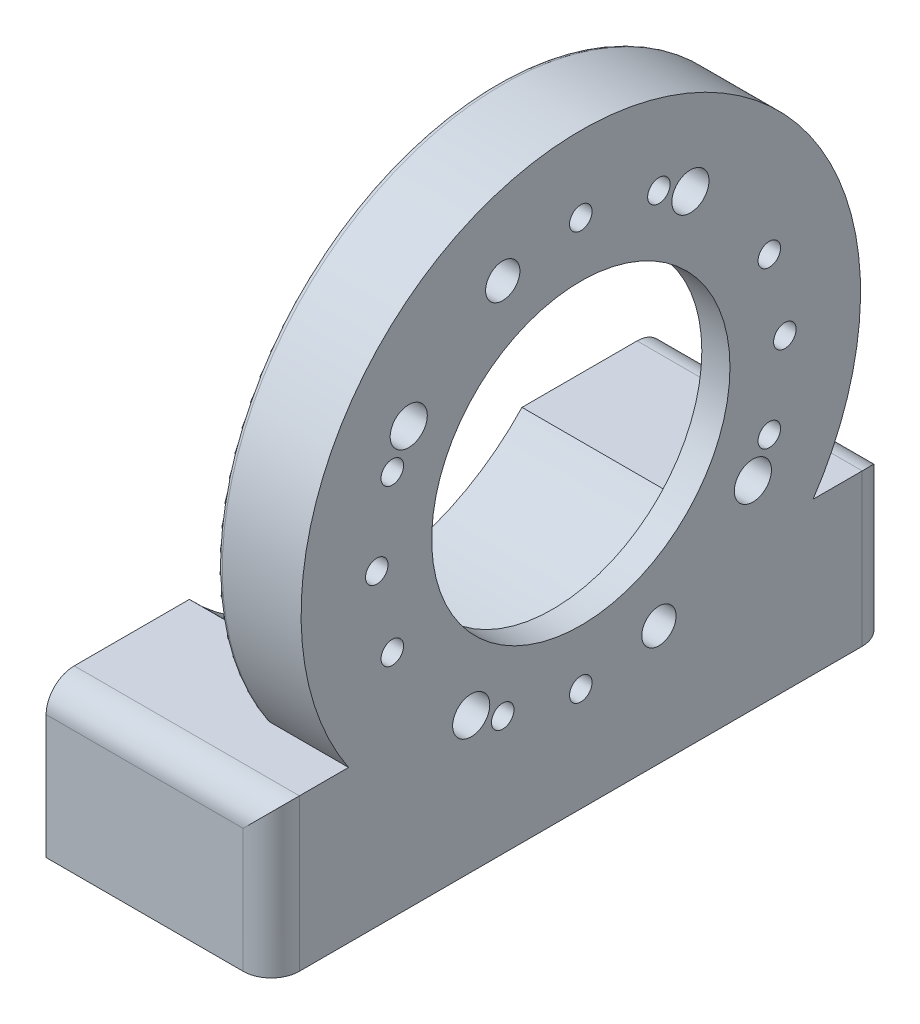
SolidWorks part; units mm, degrees
ref_plane "Front Plane" through (0, 0, 0) normal (0, 0, 1) x (1, 0, 0)
ref_plane "Top Plane" through (0, 0, 0) normal (0, 1, 0) x (1, 0, 0)
ref_plane "Right Plane" through (0, 0, 0) normal (1, 0, 0) x (0, 0, -1)
sketch "Sketch2" plane through (0, 0, 0) normal (1, 0, 0) x (0, 0, -1)
  arc A0 (-32.0764, 15.2865) -> (-34.9048, 12.4581) centre (-33.4906, 13.8723) ccw
  arc A1 (-34.9048, 12.4581) -> (-32.0764, 15.2865) centre (-33.4906, 13.8723) ccw
  arc A74 (-20.5317, -3.7195) -> (-23.1344, -1.6907) centre (-21.8331, -2.7051) ccw
  arc A75 (-23.1344, -1.6907) -> (-20.5317, -3.7195) centre (-21.8331, -2.7051) ccw
  arc A76 (-16.2541, -14.2736) -> (-18.8568, -12.2448) centre (-17.5554, -13.2592) ccw
  arc A77 (-18.8568, -12.2448) -> (-16.2541, -14.2736) centre (-17.5554, -13.2592) ccw
  arc A78 (-7.2725, -21.275) -> (-9.8752, -19.2461) centre (-8.5738, -20.2605) ccw
  arc A79 (-9.8752, -19.2461) -> (-7.2725, -21.275) centre (-8.5738, -20.2605) ccw
  arc A80 (4.0065, -22.8475) -> (1.4038, -20.8186) centre (2.7051, -21.8331) ccw
  arc A81 (1.4038, -20.8186) -> (4.0065, -22.8475) centre (2.7051, -21.8331) ccw
  arc A82 (14.5606, -18.5698) -> (11.9579, -16.541) centre (13.2592, -17.5554) ccw
  arc A83 (11.9579, -16.541) -> (14.5606, -18.5698) centre (13.2592, -17.5554) ccw
  arc A84 (21.5619, -9.5882) -> (18.9592, -7.5594) centre (20.2605, -8.5738) ccw
  arc A85 (18.9592, -7.5594) -> (21.5619, -9.5882) centre (20.2605, -8.5738) ccw
  arc A86 (23.1344, 1.6907) -> (20.5317, 3.7195) centre (21.8331, 2.7051) ccw
  arc A87 (20.5317, 3.7195) -> (23.1344, 1.6907) centre (21.8331, 2.7051) ccw
  arc A88 (18.8568, 12.2448) -> (16.2541, 14.2736) centre (17.5554, 13.2592) ccw
  arc A89 (16.2541, 14.2736) -> (18.8568, 12.2448) centre (17.5554, 13.2592) ccw
  arc A90 (9.8752, 19.2461) -> (7.2725, 21.275) centre (8.5738, 20.2605) ccw
  arc A91 (7.2725, 21.275) -> (9.8752, 19.2461) centre (8.5738, 20.2605) ccw
  arc A92 (-1.4038, 20.8186) -> (-4.0065, 22.8475) centre (-2.7051, 21.8331) ccw
  arc A93 (-4.0065, 22.8475) -> (-1.4038, 20.8186) centre (-2.7051, 21.8331) ccw
  arc A94 (-11.9579, 16.541) -> (-14.5606, 18.5698) centre (-13.2592, 17.5554) ccw
  arc A95 (-14.5606, 18.5698) -> (-11.9579, 16.541) centre (-13.2592, 17.5554) ccw
  arc A96 (-18.9592, 7.5594) -> (-21.5619, 9.5882) centre (-20.2605, 8.5738) ccw
  arc A97 (-21.5619, 9.5882) -> (-18.9592, 7.5594) centre (-20.2605, 8.5738) ccw
  arc A98 (-17.1437, -28.2395) -> (-21.8106, -32.9064) centre (-19.4771, -30.5729) ccw
  arc A99 (-21.8106, -32.9064) -> (-17.1437, -28.2395) centre (-19.4771, -30.5729) ccw
  arc A102 (32.9064, -17.1437) -> (28.2395, -21.8106) centre (30.5729, -19.4771) ccw
  arc A103 (28.2395, -21.8106) -> (32.9064, -17.1437) centre (30.5729, -19.4771) ccw
  arc A104 (21.8106, 32.9064) -> (17.1437, 28.2395) centre (19.4771, 30.5729) ccw
  arc A105 (17.1437, 28.2395) -> (21.8106, 32.9064) centre (19.4771, 30.5729) ccw
  arc A108 (-28.2395, 21.8106) -> (-32.9064, 17.1437) centre (-30.5729, 19.4771) ccw
  arc A109 (-32.9064, 17.1437) -> (-28.2395, 21.8106) centre (-30.5729, 19.4771) ccw
  arc A110 (-20.9002, 16.2921) -> (20.9002, -16.2921) centre (0, 0) ccw
  arc A111 (20.9002, -16.2921) -> (-20.9002, 16.2921) centre (0, 0) ccw
  circle A112 centre (0, 0) radius 40.5
  arc A113 (16.029, -31.334) -> (11.7156, -35.6473) centre (13.8723, -33.4906) ccw
  arc A114 (-37.6642, -1.4142) -> (-34.8358, 1.4142) centre (-36.25, 0) ccw
  arc A115 (-34.8358, 1.4142) -> (-37.6642, -1.4142) centre (-36.25, 0) ccw
  arc A116 (-34.9048, -15.2865) -> (-32.0764, -12.4581) centre (-33.4906, -13.8723) ccw
  arc A117 (-32.0764, -12.4581) -> (-34.9048, -15.2865) centre (-33.4906, -13.8723) ccw
  arc A118 (-12.4581, -32.0764) -> (-15.2865, -34.9048) centre (-13.8723, -33.4906) ccw
  arc A119 (-15.2865, -34.9048) -> (-12.4581, -32.0764) centre (-13.8723, -33.4906) ccw
  arc A120 (-1.4142, -37.6642) -> (1.4142, -34.8358) centre (0, -36.25) ccw
  arc A121 (1.4142, -34.8358) -> (-1.4142, -37.6642) centre (0, -36.25) ccw
  arc A122 (32.0764, -15.2865) -> (34.9048, -12.4581) centre (33.4906, -13.8723) ccw
  arc A123 (34.9048, -12.4581) -> (32.0764, -15.2865) centre (33.4906, -13.8723) ccw
  arc A124 (34.8358, -1.4142) -> (37.6642, 1.4142) centre (36.25, 0) ccw
  arc A125 (37.6642, 1.4142) -> (34.8358, -1.4142) centre (36.25, 0) ccw
  arc A126 (32.0764, 12.4581) -> (34.9048, 15.2865) centre (33.4906, 13.8723) ccw
  arc A127 (34.9048, 15.2865) -> (32.0764, 12.4581) centre (33.4906, 13.8723) ccw
  arc A128 (15.2865, 34.9048) -> (12.4581, 32.0764) centre (13.8723, 33.4906) ccw
  arc A129 (12.4581, 32.0764) -> (15.2865, 34.9048) centre (13.8723, 33.4906) ccw
  arc A130 (-1.4142, 34.8358) -> (1.4142, 37.6642) centre (0, 36.25) ccw
  arc A131 (1.4142, 37.6642) -> (-1.4142, 34.8358) centre (0, 36.25) ccw
  arc A132 (35.1432, 35.1432) -> (-35.1432, -35.1432) centre (0, 0) ccw
  arc A133 (-35.1432, -35.1432) -> (35.1432, 35.1432) centre (0, 0) ccw
  arc A134 (11.7156, -35.6473) -> (16.029, -31.334) centre (13.8723, -33.4906) ccw
  arc A135 (-16.029, 31.334) -> (-11.7156, 35.6473) centre (-13.8723, 33.4906) ccw
  arc A136 (-11.7156, 35.6473) -> (-16.029, 31.334) centre (-13.8723, 33.4906) ccw
extrude "Boss-Extrude1" add sketch "Sketch2" along normal blind 5 contours A112 A131 A130 A129 A128 A127 A126 A125 A124 A123 A122 A121 A120 A119 A118 A117 A116 A115 A114 A1 A0 A99 A98 A103 A102 A105 A104 A109 A108 A111 | A132 A133 A112 region at (0, 0, 39.3545) region at (0, -34.1492, -34.1492)
extrude "Boss-Extrude2" add sketch "Sketch2<5>" against normal blind 10 contours A132 A133 A112 region at (0, -34.1492, -34.1492)
sketch "Sketch2<5>" plane through (0, 0, 0) normal (1, 0, 0) x (0, 0, -1) same geometry as "Sketch2"
ref_plane "Plane1" through (0, -49.7, 0) normal (0, -1, 0) x (-1, 0, 0)
sketch "Sketch3" plane through (0, -49.7, 0) normal (0, -1, 0) x (-1, 0, 0)
  line L0 (-5, 0) -> (35, 0) construction
  line L1 (-5, 55) -> (35, 55)
  line L2 (-5, 55) -> (-5, -55)
  line L3 (-5, -55) -> (35, -55)
  line L5 (35, -55) -> (35, 0)
  line L6 (35, 55) -> (35, 0)
  line L7 (-5, 49.7) -> (-5, -49.7) construction
  dimension "D1" = 40
  dimension "D2" = 55
extrude "Boss-Extrude3" add sketch "Sketch3" along normal blind 5 and the other way blind 22 separate body
sketch "Sketch7" plane through (5, 0, 0) normal (1, 0, 0) x (0, 0, -1)
  arc A0 (-32.0764, 15.2865) -> (-34.9048, 12.4581) centre (-33.4906, 13.8723) ccw
  arc A1 (-34.9048, 12.4581) -> (-32.0764, 15.2865) centre (-33.4906, 13.8723) ccw
  arc A2 (-20.5317, -3.7195) -> (-23.1344, -1.6907) centre (-21.8331, -2.7051) ccw
  arc A3 (-23.1344, -1.6907) -> (-20.5317, -3.7195) centre (-21.8331, -2.7051) ccw
  arc A4 (-16.2541, -14.2736) -> (-18.8568, -12.2448) centre (-17.5554, -13.2592) ccw
  arc A5 (-18.8568, -12.2448) -> (-16.2541, -14.2736) centre (-17.5554, -13.2592) ccw
  arc A6 (-7.2725, -21.275) -> (-9.8752, -19.2461) centre (-8.5738, -20.2605) ccw
  arc A7 (-9.8752, -19.2461) -> (-7.2725, -21.275) centre (-8.5738, -20.2605) ccw
  arc A8 (4.0065, -22.8475) -> (1.4038, -20.8186) centre (2.7051, -21.8331) ccw
  arc A9 (1.4038, -20.8186) -> (4.0065, -22.8475) centre (2.7051, -21.8331) ccw
  arc A10 (14.5606, -18.5698) -> (11.9579, -16.541) centre (13.2592, -17.5554) ccw
  arc A11 (11.9579, -16.541) -> (14.5606, -18.5698) centre (13.2592, -17.5554) ccw
  arc A12 (21.5619, -9.5882) -> (18.9592, -7.5594) centre (20.2605, -8.5738) ccw
  arc A13 (18.9592, -7.5594) -> (21.5619, -9.5882) centre (20.2605, -8.5738) ccw
  arc A14 (23.1344, 1.6907) -> (20.5317, 3.7195) centre (21.8331, 2.7051) ccw
  arc A15 (20.5317, 3.7195) -> (23.1344, 1.6907) centre (21.8331, 2.7051) ccw
  arc A16 (18.8568, 12.2448) -> (16.2541, 14.2736) centre (17.5554, 13.2592) ccw
  arc A17 (16.2541, 14.2736) -> (18.8568, 12.2448) centre (17.5554, 13.2592) ccw
  arc A18 (9.8752, 19.2461) -> (7.2725, 21.275) centre (8.5738, 20.2605) ccw
  arc A19 (7.2725, 21.275) -> (9.8752, 19.2461) centre (8.5738, 20.2605) ccw
  arc A20 (-1.4038, 20.8186) -> (-4.0065, 22.8475) centre (-2.7051, 21.8331) ccw
  arc A21 (-4.0065, 22.8475) -> (-1.4038, 20.8186) centre (-2.7051, 21.8331) ccw
  arc A22 (-11.9579, 16.541) -> (-14.5606, 18.5698) centre (-13.2592, 17.5554) ccw
  arc A23 (-14.5606, 18.5698) -> (-11.9579, 16.541) centre (-13.2592, 17.5554) ccw
  arc A24 (-18.9592, 7.5594) -> (-21.5619, 9.5882) centre (-20.2605, 8.5738) ccw
  arc A25 (-21.5619, 9.5882) -> (-18.9592, 7.5594) centre (-20.2605, 8.5738) ccw
  arc A26 (-17.1437, -28.2395) -> (-21.8106, -32.9064) centre (-19.4771, -30.5729) ccw
  arc A27 (-21.8106, -32.9064) -> (-17.1437, -28.2395) centre (-19.4771, -30.5729) ccw
  arc A28 (32.9064, -17.1437) -> (28.2395, -21.8106) centre (30.5729, -19.4771) ccw
  arc A29 (28.2395, -21.8106) -> (32.9064, -17.1437) centre (30.5729, -19.4771) ccw
  arc A30 (21.8106, 32.9064) -> (17.1437, 28.2395) centre (19.4771, 30.5729) ccw
  arc A31 (17.1437, 28.2395) -> (21.8106, 32.9064) centre (19.4771, 30.5729) ccw
  arc A32 (-28.2395, 21.8106) -> (-32.9064, 17.1437) centre (-30.5729, 19.4771) ccw
  arc A33 (-32.9064, 17.1437) -> (-28.2395, 21.8106) centre (-30.5729, 19.4771) ccw
  arc A34 (-20.9002, 16.2921) -> (20.9002, -16.2921) centre (0, 0) ccw
  arc A35 (20.9002, -16.2921) -> (-20.9002, 16.2921) centre (0, 0) ccw
  circle A36 centre (0, 0) radius 40.5
  arc A37 (16.029, -31.334) -> (11.7156, -35.6473) centre (13.8723, -33.4906) ccw
  arc A38 (-37.6642, -1.4142) -> (-34.8358, 1.4142) centre (-36.25, 0) ccw
  arc A39 (-34.8358, 1.4142) -> (-37.6642, -1.4142) centre (-36.25, 0) ccw
  arc A40 (-34.9048, -15.2865) -> (-32.0764, -12.4581) centre (-33.4906, -13.8723) ccw
  arc A41 (-32.0764, -12.4581) -> (-34.9048, -15.2865) centre (-33.4906, -13.8723) ccw
  arc A42 (-12.4581, -32.0764) -> (-15.2865, -34.9048) centre (-13.8723, -33.4906) ccw
  arc A43 (-15.2865, -34.9048) -> (-12.4581, -32.0764) centre (-13.8723, -33.4906) ccw
  arc A44 (-1.4142, -37.6642) -> (1.4142, -34.8358) centre (0, -36.25) ccw
  arc A45 (1.4142, -34.8358) -> (-1.4142, -37.6642) centre (0, -36.25) ccw
  arc A46 (32.0764, -15.2865) -> (34.9048, -12.4581) centre (33.4906, -13.8723) ccw
  arc A47 (34.9048, -12.4581) -> (32.0764, -15.2865) centre (33.4906, -13.8723) ccw
  arc A48 (34.8358, -1.4142) -> (37.6642, 1.4142) centre (36.25, 0) ccw
  arc A49 (37.6642, 1.4142) -> (34.8358, -1.4142) centre (36.25, 0) ccw
  arc A50 (32.0764, 12.4581) -> (34.9048, 15.2865) centre (33.4906, 13.8723) ccw
  arc A51 (34.9048, 15.2865) -> (32.0764, 12.4581) centre (33.4906, 13.8723) ccw
  arc A52 (15.2865, 34.9048) -> (12.4581, 32.0764) centre (13.8723, 33.4906) ccw
  arc A53 (12.4581, 32.0764) -> (15.2865, 34.9048) centre (13.8723, 33.4906) ccw
  arc A54 (-1.4142, 34.8358) -> (1.4142, 37.6642) centre (0, 36.25) ccw
  arc A55 (1.4142, 37.6642) -> (-1.4142, 34.8358) centre (0, 36.25) ccw
  arc A56 (35.1432, 35.1432) -> (-35.1432, -35.1432) centre (0, 0) ccw
  arc A57 (-35.1432, -35.1432) -> (35.1432, 35.1432) centre (0, 0) ccw
  arc A58 (11.7156, -35.6473) -> (16.029, -31.334) centre (13.8723, -33.4906) ccw
  arc A59 (-16.029, 31.334) -> (-11.7156, 35.6473) centre (-13.8723, 33.4906) ccw
  arc A60 (-11.7156, 35.6473) -> (-16.029, 31.334) centre (-13.8723, 33.4906) ccw
  circle M7 centre (13.8723, -33.4906) radius 3.05
  circle M13 centre (0, -36.25) radius 2
  circle M14 centre (-13.8723, -33.4906) radius 2
  circle M18 centre (-19.4771, -30.5729) radius 3.3
extrude "Cut-Extrude8" cut sketch "Sketch2<11>" against normal blind 50 contours A112 A136 A135 A134 A113 A131 A130 A129 A128 A127 A126 A125 A124 A123 A122 A121 A120 A119 A118 A117 A116 A115 A114 A1 A0 A99 A98 A103 A102 A105 A104 A109 A108 A111 region at (0, 0, 39.3545)
sketch "Sketch2<11>" plane through (0, 0, 0) normal (1, 0, 0) x (0, 0, -1) same geometry as "Sketch2"
extrude "Cut-Extrude9" cut sketch "Sketch7" against normal through all contours M13 | M7 | M14 | M18 | A37 A58 region at (5, -30.5729, 19.4771) region at (5, -33.4906, -13.8723) region at (5, -33.4906, 13.8723) region at (5, -36.25, 0)
fillet "Fillet1" radius 5 4 edges at (5, -41.2, -55) (5, -41.2, 55) (-15, -27.7, 55) (-15, -27.7, -55)
fillet "Fillet2" radius 2 1 edges at (-10, 0, -40.5)
fillet "Fillet3" radius 1 1 edges at (-10, 0, -49.7)
combine bodies "Combine1" operation type add bodies to combine 104 112
